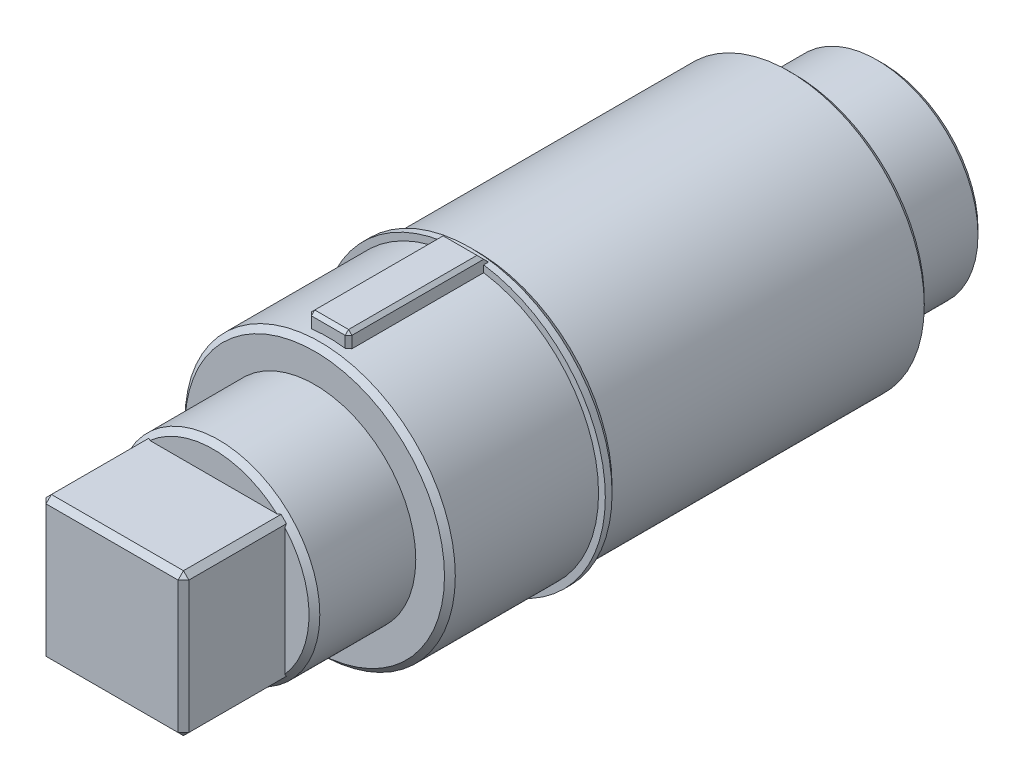
SolidWorks part; units mm, degrees
ref_plane "Front Plane" through (0, 0, 0) normal (0, 0, 1) x (1, 0, 0)
ref_plane "Top Plane" through (0, 0, 0) normal (0, 1, 0) x (1, 0, 0)
ref_plane "Right Plane" through (0, 0, 0) normal (1, 0, 0) x (0, 0, -1)
sketch "Sketch1" plane through (0, 0, 0) normal (0, 0, 1) x (1, 0, 0)
  circle A0 centre (0, 0) radius 20
  dimension "D1" = 40
extrude "Boss-Extrude1" add sketch "Sketch1" along normal mid plane 114
sketch "Sketch2" plane through (0, 0, -57) normal (0, 0, -1) x (-1, 0, 0)
  circle A0 centre (0, 0) radius 14.95
  circle A1 centre (0, 0) radius 20 construction
  circle A2 centre (0, 0) radius 20
  dimension "D1" = 29.9
extrude "Cut-Extrude1" cut sketch "Sketch2" against normal blind 13
chamfer "Chamfer1" distance 0.8 angle 45 2 edges at (-14.95, 0, -57) (-20, 0, -44)
sketch "Sketch3" plane through (0, 0, 57) normal (0, 0, 1) x (1, 0, 0)
  circle A0 centre (0, 0) radius 20 construction
  circle A1 centre (0, 0) radius 20
  circle A2 centre (0, 0) radius 14.95
  dimension "D1" = 29.9
extrude "Cut-Extrude2" cut sketch "Sketch3" against normal blind 30
sketch "Sketch4" plane through (0, 0, 57) normal (0, 0, 1) x (1, 0, 0)
  line L1 (-10.5712, -10.5712) -> (10.5712, -10.5712)
  line L2 (-10.5712, -10.5712) -> (-10.5712, 10.5712)
  line L3 (-10.5712, 10.5712) -> (10.5712, 10.5712)
  line L4 (10.5712, -10.5712) -> (10.5712, 10.5712)
  line L5 (-10.5712, -10.5712) -> (10.5712, 10.5712) construction
  line L6 (-10.5712, 10.5712) -> (10.5712, -10.5712) construction
  circle A0 centre (0, 0) radius 14.95 construction
  circle A1 centre (0, 0) radius 14.95 construction
  circle A2 centre (0, 0) radius 14.95
  point P0 (0, 0)
  circle M1 centre (0, 0) radius 14.95
extrude "Cut-Extrude4" cut sketch "Sketch4" against normal blind 15 contours L3 M1 | L4 M1 | L2 M1 | L1 M1
chamfer "Chamfer2" distance 0.8 angle 45 9 edges at (-10.5712, 0, 57) (-10.5712, 10.5712, 49.5) (0, 10.5712, 57) (-10.5712, -10.5712, 49.5) (0, -10.5712, 57) (10.5712, -10.5712, 49.5) (10.5712, 0, 57) (10.5712, 10.5712, 49.5) (20, 0, 27)
chamfer "Chamfer3" distance 0.8 angle 45 8 edges at (0, 14.95, 42) (0, -14.95, 42) (14.95, 0, 42) (-14.95, 0, 42) (-10.1712, 10.1712, 42) (-10.1712, -10.1712, 42) (10.1712, -10.1712, 42) (10.1712, 10.1712, 42)
ref_plane "Plane1" through (0, 0, 5) normal (0, 0, 1) x (1, 0, 0)
sketch "Sketch5" plane through (0, 0, 5) normal (0, 0, 1) x (1, 0, 0)
  line L0 (0, -1000) -> (0, 49000) construction
  line L2 (-3, 18) -> (3, 18)
  line L3 (-3, 18) -> (-3, 22)
  line L4 (-3, 22) -> (3, 22)
  line L5 (3, 18) -> (3, 22)
  line L6 (-3, 18) -> (3, 22) construction
  line L7 (-3, 22) -> (3, 18) construction
  circle A0 centre (0, 0) radius 20 construction
  point P1 (0, 20)
  dimension "D1" = 6
  dimension "D2" = 4
extrude "Boss-Extrude2" add sketch "Sketch5" along normal blind 20
sketch "Sketch6" plane through (0, 0, 5) normal (0, 0, 1) x (1, 0, 0)
  circle A2 centre (0, 0) radius 21
  circle A3 centre (0, 0) radius 21
  dimension "D1" = 1
extrude "Boss-Extrude3" add sketch "Sketch6" against normal blind 1
chamfer "Chamfer4" distance 1 angle 45 1 edges at (20, 0, 4)
chamfer "Chamfer5" distance 0.5 angle 45 6 edges at (0, 22, 5) (3, 20.8869, 25) (-3, 20.8869, 25) (-3, 22, 15) (0, 22, 25) (3, 22, 15)
chamfer "Chamfer6" distance 0.7 angle 45 1 edges at (0, 21, 5)
